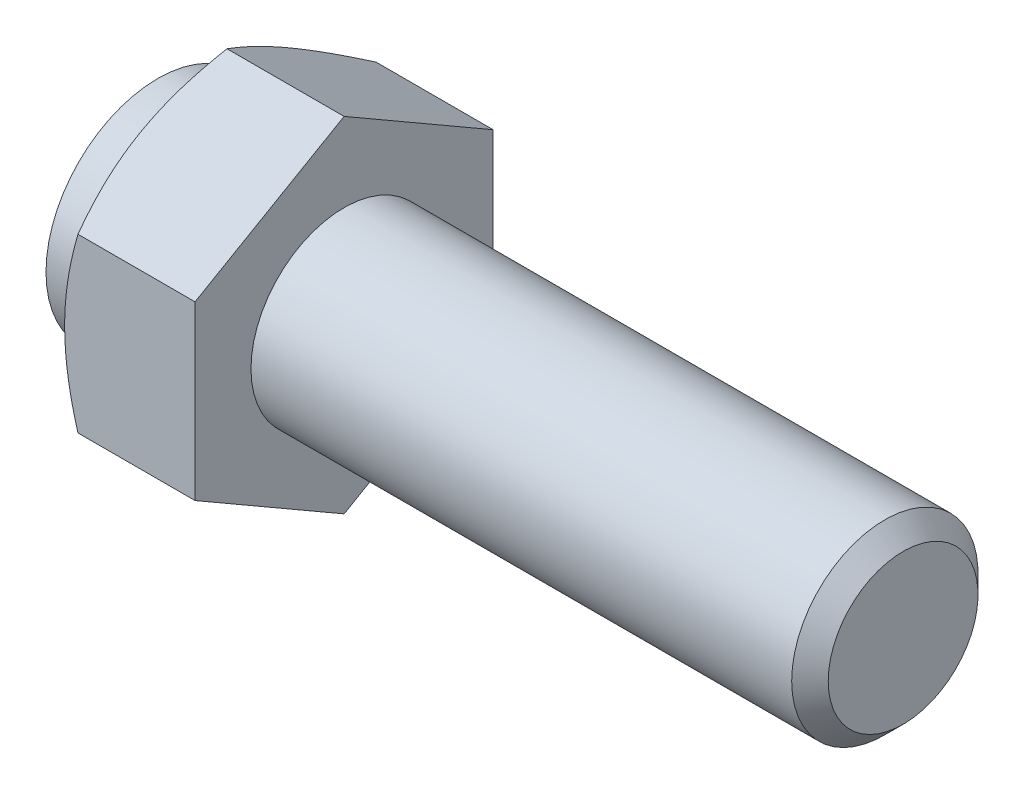
SolidWorks part; units mm, degrees
ref_plane "前视基准面" through (0, 0, 0) normal (0, 0, 1) x (1, 0, 0)
ref_plane "上视基准面" through (0, 0, 0) normal (0, 1, 0) x (1, 0, 0)
ref_plane "右视基准面" through (0, 0, 0) normal (1, 0, 0) x (0, 0, -1)
sketch "草图1" plane through (0, 0, 0) normal (0, 0, 1) x (1, 0, 0)
  line L0 (-5, 0) -> (-5, 3)
  line L1 (-5, 3) -> (-3.5, 3)
  line L2 (-3.5, 3) -> (-3.5, 4)
  line L3 (-3.5, 4) -> (-3.0381, 4.8)
  line L4 (-3.0381, 4.8) -> (0, 4.8)
  line L5 (0, 4.8) -> (0, 2.5)
  line L6 (0, 2.5) -> (14.5095, 2.5)
  line L7 (14.5095, 2.5) -> (15, 2.0095)
  line L8 (15, 2.0095) -> (15, 0)
  line L9 (15, 0) -> (-5, 0)
  line L10 (15, 0) -> (-5, 0) construction
revolve "旋转1" add sketch "草图1" angle 360 about L10 reverse direction yes
cosmetic thread "装饰螺纹线1" parameters "D1"=13.4, "D2"=4.019
ref_plane "基准面1" through (7.5, 0, 0) normal (1, 0, 0) x (0, 0, -1)
ref_plane "基准面2" through (15, 0, 0) normal (1, 0, 0) x (0, 0, -1)
sketch "草图2" plane through (0, 0, 0) normal (1, 0, 0) x (0, 0, -1)
  line L0 (-9.2, -9.2) -> (9.2, -9.2)
  line L1 (9.2, -9.2) -> (9.2, 9.2)
  line L2 (9.2, 9.2) -> (-9.2, 9.2)
  line L3 (-9.2, 9.2) -> (-9.2, -9.2)
  line L4 (-4, 2.3094) -> (-4, -2.3094)
  line L5 (-4, -2.3094) -> (0, -4.6188)
  line L6 (0, -4.6188) -> (4, -2.3094)
  line L7 (4, -2.3094) -> (4, 2.3094)
  line L8 (4, 2.3094) -> (0, 4.6188)
  line L9 (0, 4.6188) -> (-4, 2.3094)
extrude "切除-拉伸1" cut sketch "草图2" against normal blind 5
ref_plane "基准面3" through (-5, 0, 0) normal (1, 0, 0) x (0, 0, -1)
ref_plane "ustb_n XY" through (7.5, 0, 0) normal (1, 0, 0) x (0, 0, -1)
ref_plane "ustb_n XZ" through (0, 0, 0) normal (0, -1, 0) x (1, 0, 0)
ref_plane "ustb_n YZ" through (0, 0, 0) normal (0, 0, -1) x (-1, 0, 0)
ref_axis "ustb_n X" through (7.5, 0, 80.9) along (0, 0, -1)
ref_axis "ustb_n Y" through (7.5, -50, 0) along (0, 1, 0)
ref_axis "ustb_n Z" through (80.9, 0, 0) along (-1, 0, 0)
sketch3d "ustb_n"
  point P0 (7.5, 0, 0)
ref_plane "cp XY" through (-5, 0, 0) normal (1, 0, 0) x (0, 0, -1)
ref_plane "cp XZ" through (0, 0, 0) normal (0, -1, 0) x (1, 0, 0)
ref_plane "cp YZ" through (0, 0, 0) normal (0, 0, -1) x (-1, 0, 0)
ref_axis "cp X" through (-5, 0, 80.9) along (0, 0, -1)
ref_axis "cp Y" through (-5, -50, 0) along (0, 1, 0)
ref_axis "cp Z" through (80.9, 0, 0) along (-1, 0, 0)
sketch3d "cp"
  point P0 (-5, 0, 0)
